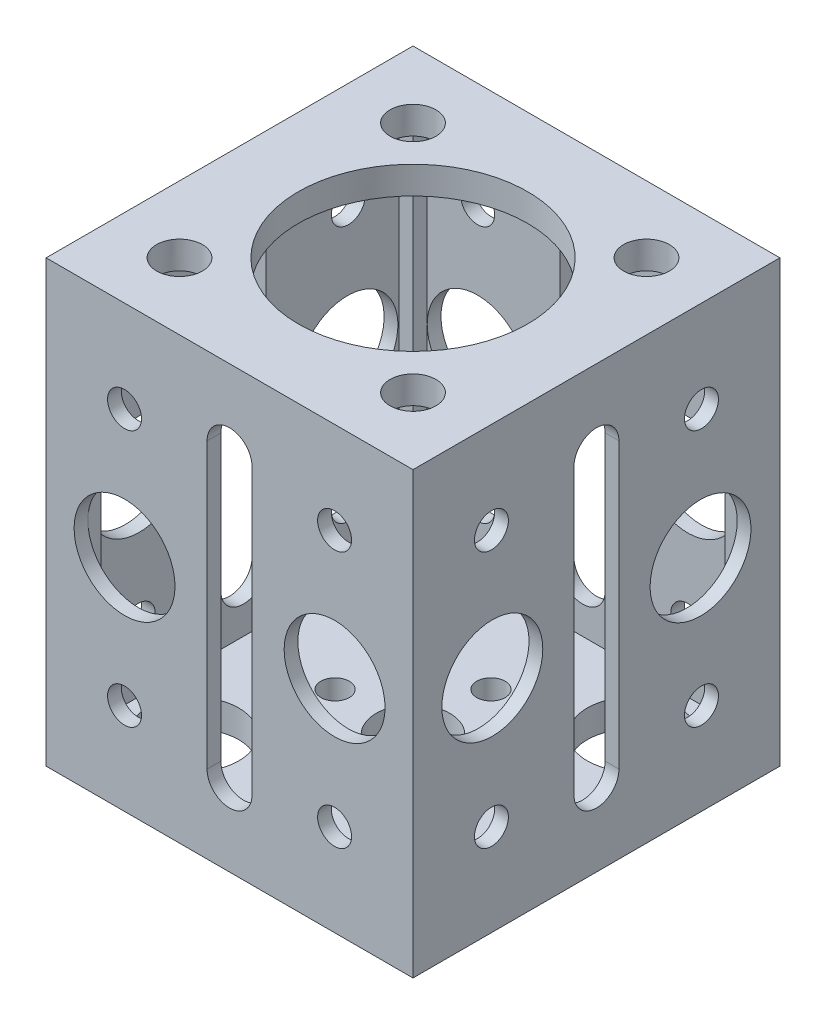
SolidWorks part; units mm, degrees
ref_plane "前视基准面" through (0, 0, 0) normal (0, 0, 1) x (1, 0, 0)
ref_plane "上视基准面" through (0, 0, 0) normal (0, 1, 0) x (1, 0, 0)
ref_plane "右视基准面" through (0, 0, 0) normal (1, 0, 0) x (0, 0, -1)
other "Configuration Table"
sketch "草图1" plane through (0, 0, 0) normal (0, 1, 0) x (1, 0, 0)
  line L0 (0, 8.5) -> (0, -8.5)
  line L1 (-20, 20) -> (20, 20)
  line L2 (-20, 20) -> (-20, -20)
  line L3 (-20, -20) -> (20, -20)
  line L4 (20, 20) -> (20, -20)
  line L5 (-20, 20) -> (20, -20) construction
  line L6 (-20, -20) -> (20, 20) construction
  line L7 (0, 0) -> (-20, 0) construction
  line L8 (-18.5, -18.5) -> (18.5, -18.5)
  line L9 (18.5, 18.5) -> (18.5, -18.5)
  line L10 (-18.5, 18.5) -> (18.5, 18.5)
  line L11 (-18.5, 18.5) -> (-18.5, -18.5)
  circle A0 centre (0, 0) radius 12.6
  circle A1 centre (0, 8.5) radius 1.55
  circle A3 centre (0, 0) radius 4
  circle A4 centre (8.5, 0) radius 1.55
  circle A5 centre (0, -8.5) radius 1.55
  circle A6 centre (-8.5, 0) radius 1.55
  point P0 (0, 0)
  point P11 (0, 0)
  point P23 (0, 0)
  dimension "D4" = 25.2
  dimension "D6" = 3.1
  dimension "D7" = 8
  dimension "D8" = 4
  dimension "D1" = 40
  dimension "D2" = 40
  dimension "D3" = 20
  dimension "D5" = 17
  dimension "D10" = 1.5
  dimension "D9" = 1.5
extrude "凸台-拉伸2" add sketch "草图1" against normal blind 3 contours L2 L3 L4 L1 | A6 | A5 | A1 | A4
extrude "切除-拉伸1" cut sketch "草图1<6>" against normal blind 1.5 contours L0 A3 | L0 A3 region at (1.6977, 0, 0) region at (-1.6977, 0, 0)
sketch "草图1<6>" plane through (0, 0, 0) normal (0, 1, 0) x (1, 0, 0) same geometry as "草图1"
sketch "草图2" plane through (0, 0, 0) normal (0, 1, 0) x (1, 0, 0)
  line L0 (-20, -20) -> (20, -20) construction
  line L1 (20, 20) -> (20, -20) construction
  line L2 (-20, 20) -> (-20, -20) construction
  line L3 (-20, 20) -> (20, 20) construction
  line L4 (-20, -20) -> (20, -20)
  line L5 (20, 20) -> (20, -20)
  line L6 (-20, 20) -> (-20, -20)
  line L7 (-20, 20) -> (20, 20)
  line L8 (0, 0) -> (38.7801, 0) construction
  line L9 (-20, 20) -> (-17, 20)
  line L10 (-20, 20) -> (-20, 17)
  line L11 (-20, 17) -> (-17, 17)
  line L12 (-17, 20) -> (-17, 17)
  line L13 (0, 0) -> (0, 17.8693) construction
  line L14 (20, -17) -> (17, -17)
  line L15 (20, 20) -> (17, 20)
  line L16 (20, 20) -> (20, 17)
  line L17 (20, 17) -> (17, 17)
  line L18 (17, 20) -> (17, 17)
  line L19 (17, -20) -> (17, -17)
  line L20 (20, -20) -> (17, -20)
  line L21 (20, -20) -> (20, -17)
  line L22 (-20, -20) -> (-20, -17)
  line L23 (-20, -20) -> (-17, -20)
  line L24 (-17, -20) -> (-17, -17)
  line L25 (-20, -17) -> (-17, -17)
  circle A0 centre (0, -8.5) radius 1.55 construction
  circle A1 centre (8.5, 0) radius 1.55 construction
  circle A2 centre (0, 8.5) radius 1.55 construction
  circle A3 centre (0, 0) radius 4 construction
  circle A4 centre (-8.5, 0) radius 1.55 construction
  circle A5 centre (0, -8.5) radius 1.55
  circle A6 centre (8.5, 0) radius 1.55
  circle A7 centre (0, 8.5) radius 1.55
  circle A8 centre (0, 0) radius 4
  circle A9 centre (-8.5, 0) radius 1.55
  point P35 (18.5, -17)
  line M9 (20, 20) -> (-20, 20)
  line M10 (-20, 20) -> (-20, -20)
  line M11 (-20, -20) -> (20, -20)
  line M12 (20, -20) -> (20, 20)
  dimension "D1" = 3
  dimension "D2" = 3
  dimension "D3" = 34
  dimension "D4" = 34
  dimension "D5" = 34
  dimension "D6" = 34
extrude "凸台-拉伸7" add sketch "草图2" along normal blind 45 contours L12 L7 L11 M10 | L18 L17 M9 M12 | L19 L4 L14 M12 | L25 L24 M10 M11 region at (-18.5, 0, 18.5) region at (18.5, 0, 18.5) region at (-18.5, 0, -18.5) region at (18.5, 0, -18.5)
sketch "草图5" plane through (-20, 0, 0) normal (-1, 0, 0) x (0, 0, 1)
  line L0 (20, -3) -> (20, 45) construction
  line L1 (-20, -3) -> (-20, 45) construction
  line L2 (20, -3) -> (20, 45)
  line L3 (-20, -3) -> (-20, 45)
  line L4 (-17, 0) -> (-17, 45)
  line L5 (-17, 45) -> (-17, 0) construction
  line L7 (-20, 45) -> (20, 45)
  line L8 (-20, 45) -> (-20, 42)
  line L9 (-20, 42) -> (20, 42)
  line L10 (20, 45) -> (20, 42)
extrude "凸台-拉伸8" add sketch "草图5" against normal blind 40 contours L8 L9 L10 L7
sketch "草图6" plane through (0, 45, 0) normal (0, 1, 0) x (1, 0, 0)
  line L0 (-20, -20) -> (0, -20)
  line L1 (0, -20) -> (0, 0)
  line L4 (20, -20) -> (20, 20)
  line L5 (20, 20) -> (-20, 20)
  line L6 (-20, 20) -> (-20, -20)
  line L7 (-20, -20) -> (20, -20)
  line L8 (20, -20) -> (20, 20)
  line L9 (20, 20) -> (-20, 20)
  line L10 (-20, 20) -> (-20, -20)
  line L11 (-20, -20) -> (20, -20)
  circle A0 centre (0, 0) radius 12.5
  dimension "D1" = 0
extrude "切除-拉伸2" cut sketch "草图6" against normal blind 4 contours A0 region at (-8.5888, 45, -8.5888)
sketch "草图7" plane through (0, -3, 0) normal (0, -1, 0) x (1, 0, 0)
  line L1 (-20, -20) -> (0, -20)
  line L2 (-20, -20) -> (-20, 0)
  line L3 (-20, 0) -> (0, 0)
  line L4 (-20, -20) -> (20, -20)
  line L5 (20, -20) -> (20, 20)
  line L6 (20, 20) -> (-20, 20)
  line L7 (-20, 20) -> (-20, -20)
  line L8 (-20, -20) -> (20, -20)
  line L9 (20, -20) -> (20, 20)
  line L10 (20, 20) -> (-20, 20)
  line L11 (-20, 20) -> (-20, -20)
  line L12 (0, -20) -> (0, 0)
  circle A0 centre (0, 0) radius 4
  dimension "D1" = 0
extrude "切除-拉伸3" cut sketch "草图7" against normal blind 4 contours L12 A0 L3 | L3 A0 L12 region at (-1.6977, -3, -1.6977) region at (0.5659, -3, 0.5659)
sketch "草图8" plane through (0, -3, 0) normal (0, -1, 0) x (1, 0, 0)
  line L0 (-20, 20) -> (0, 0) construction
  line L1 (0, 0) -> (20, 20) construction
  line L2 (-20, -20) -> (-20, 20) construction
  circle A0 centre (-12, 12) radius 5
  circle A1 centre (12, 12) radius 5
  circle A2 centre (12, -12) radius 5
  circle A3 centre (-12, -12) radius 5
  point P19 (0, 0)
  dimension "D1" = 8
  dimension "D2" = 4
extrude "切除-拉伸4" cut sketch "草图8" against normal blind 4
sketch "草图9" plane through (0, 45, 0) normal (0, 1, 0) x (1, 0, 0)
  line L0 (-20, 20) -> (0, 0) construction
  line L1 (0, 0) -> (20, 20) construction
  line L4 (20, -20) -> (20, 20)
  line L5 (20, 20) -> (-20, 20)
  line L6 (-20, 20) -> (-20, -20)
  line L7 (-20, -20) -> (20, -20)
  line L8 (20, -20) -> (20, 20)
  line L9 (20, 20) -> (-20, 20)
  line L10 (-20, 20) -> (-20, -20)
  line L11 (-20, -20) -> (20, -20)
  circle A0 centre (-12.7279, 12.7279) radius 2.5
  circle A1 centre (0, 0) radius 12.5 construction
  circle A2 centre (12.7279, 12.7279) radius 2.5
  circle A3 centre (12.7279, -12.7279) radius 2.5
  circle A4 centre (-12.7279, -12.7279) radius 2.5
  point P19 (0, 0)
  dimension "D2" = 18
  dimension "D3" = 4
  dimension "D1" = 0
extrude "切除-拉伸5" cut sketch "草图9" against normal blind 4 contours A0 | A4 | A2 | A3
sketch "草图10" plane through (0, 0, 0) normal (0, 1, 0) x (1, 0, 0)
  line L0 (20, -17) -> (17, -17) construction
  line L1 (20, 17) -> (18.5, 17)
  line L2 (20, 17) -> (20, -17)
  line L3 (20, -17) -> (18.5, -17)
  line L4 (18.5, 17) -> (18.5, -17)
  line L5 (17, -20) -> (-17, -20)
  line L6 (17, -20) -> (17, -18.5)
  line L7 (17, -18.5) -> (-17, -18.5)
  line L8 (-17, -20) -> (-17, -18.5)
  line L9 (-20, -17) -> (-20, 17)
  line L10 (-20, -17) -> (-18.5, -17)
  line L11 (-18.5, -17) -> (-18.5, 17)
  line L12 (-20, 17) -> (-18.5, 17)
  line L13 (-17, 20) -> (17, 20)
  line L14 (-17, 20) -> (-17, 18.5)
  line L15 (-17, 18.5) -> (17, 18.5)
  line L16 (17, 20) -> (17, 18.5)
  point P25 (0, 0)
  dimension "D1" = 4
extrude "凸台-拉伸10" add sketch "草图10" along normal blind 45
sketch "草图20" plane through (0, 0, 18.5) normal (0, 0, -1) x (-1, 0, 0)
  line L0 (0, 0) -> (0, 42)
  line L1 (-17, 0) -> (17, 0) construction
  line L2 (-20, -3) -> (-20, 45) construction
  line L3 (0, 0) -> (0, 3)
  line L4 (0, 3) -> (0, 5.5)
  line L5 (0, 21) -> (4.1437, 21)
  line L6 (-2.45, 36.5) -> (-2.45, 5.5)
  line L7 (2.45, 36.5) -> (2.45, 5.5)
  line L8 (-20, 45) -> (20, 45) construction
  line L9 (20, -3) -> (-20, -3) construction
  arc A1 (-2.45, 5.5) -> (2.45, 5.5) centre (0, 5.5) ccw
  arc A2 (-2.45, 36.5) -> (2.45, 36.5) centre (0, 36.5) cw
  point P10 (0, 45)
  point P13 (0, 38.95)
  point P20 (0, -3)
  point P21 (0, 3)
  dimension "D1" = 90
  dimension "D3" = 2.45
  dimension "D2" = 20
  dimension "D4" = 5.5
extrude "切除-拉伸12" cut sketch "草图20" against normal blind 4 and the other way through all contours L7 A1 L6 A2
sketch "草图24" plane through (20, 0, 0) normal (1, 0, 0) x (0, 0, -1)
  line L0 (0, -3) -> (0, 3)
  line L1 (0, 21) -> (-20, 21) construction
  line L2 (20, -3) -> (-20, -3) construction
  line L3 (0, 3) -> (0, 5.5)
  line L4 (0, -3) -> (0, 0)
  line L5 (0, 0) -> (0, 42)
  line L6 (0, 21) -> (5.4047, 21)
  line L7 (-2.45, 36.5) -> (-2.45, 5.5)
  line L8 (2.45, 5.5) -> (2.45, 36.5)
  line L9 (-20, 45) -> (20, 45) construction
  line L12 (-11.35, -3) -> (-11.35, 45) construction
  line L13 (-11.35, 21) -> (-11.35, 49) construction
  line L16 (20, -3) -> (20, 45)
  line L17 (20, 45) -> (-20, 45)
  line L18 (-20, 45) -> (-20, -3)
  line L19 (-20, -3) -> (20, -3)
  line L20 (20, -3) -> (20, 45)
  line L21 (20, 45) -> (-20, 45)
  line L22 (-20, 45) -> (-20, -3)
  line L23 (-20, -3) -> (20, -3)
  arc A0 (-2.45, 5.5) -> (2.45, 5.5) centre (0, 5.5) ccw
  arc A1 (-2.45, 36.5) -> (2.45, 36.5) centre (0, 36.5) cw
  circle A2 centre (-11.45, 35) radius 1.85
  circle A3 centre (-11.45, 7) radius 1.85
  circle A4 centre (11.45, 7) radius 1.85
  circle A5 centre (11.45, 35) radius 1.85
  circle A6 centre (-11.35, 21) radius 5.5
  circle A7 centre (11.35, 21) radius 5.5
  point P7 (0, 38.95)
  point P13 (0, 45)
  point P18 (0, 3.05)
  point P37 (-11.45, 35)
  dimension "D1" = 3
  dimension "D3" = 9
  dimension "D4" = 3.7
  dimension "D6" = 10
  dimension "D7" = 8.65
  dimension "D8" = 2.45
  dimension "D2" = 8.5
  dimension "D5" = 0
extrude "切除-拉伸13" cut sketch "草图24" along normal blind 4 and the other way through all contours L7 A0 L8 A1
extrude "切除-拉伸15" cut sketch "草图24<5>" along normal blind 10 and the other way through all contours A2 | A5 | A6 | A7 | A3 | A4
sketch "草图24<5>" plane through (20, 0, 0) normal (1, 0, 0) x (0, 0, -1) same geometry as "草图24"
sketch "草图25" plane through (0, 0, -20) normal (0, 0, -1) x (-1, 0, 0)
  line L0 (-11.45, -3) -> (-11.45, 45) construction
  line L1 (-2.45, 36.5) -> (-2.45, 5.5) construction
  line L2 (-11.45, 21) -> (-31.2071, 21) construction
  line L3 (-11.45, 45) -> (-11.45, 35) construction
  line L4 (20, -3) -> (20, 45)
  line L5 (20, 45) -> (-20, 45)
  line L6 (-20, 45) -> (-20, -3)
  line L7 (-20, -3) -> (20, -3)
  line L8 (20, -3) -> (20, 45)
  line L9 (20, 45) -> (-20, 45)
  line L10 (-20, 45) -> (-20, -3)
  line L11 (-20, -3) -> (20, -3)
  line L12 (0, 0) -> (0, 45) construction
  line L13 (-2.45, 36.5) -> (-2.45, 5.5)
  circle A0 centre (-11.45, 21) radius 5.5
  circle A1 centre (-11.45, 35) radius 1.85
  circle A2 centre (11.45, 35) radius 1.85
  circle A3 centre (11.45, 7) radius 1.85
  circle A4 centre (-11.45, 7) radius 1.85
  circle A5 centre (11.45, 21) radius 5.5
  dimension "D3" = 10
  dimension "D4" = 11
  dimension "D2" = 9
  dimension "D1" = 0
extrude "切除-拉伸16" cut sketch "草图25" along normal blind 10 and the other way through all contours A0 | A5 | A1 | A4 | A3 | A2 region at (11.45, 21, -20) region at (-11.45, 21, -20)
